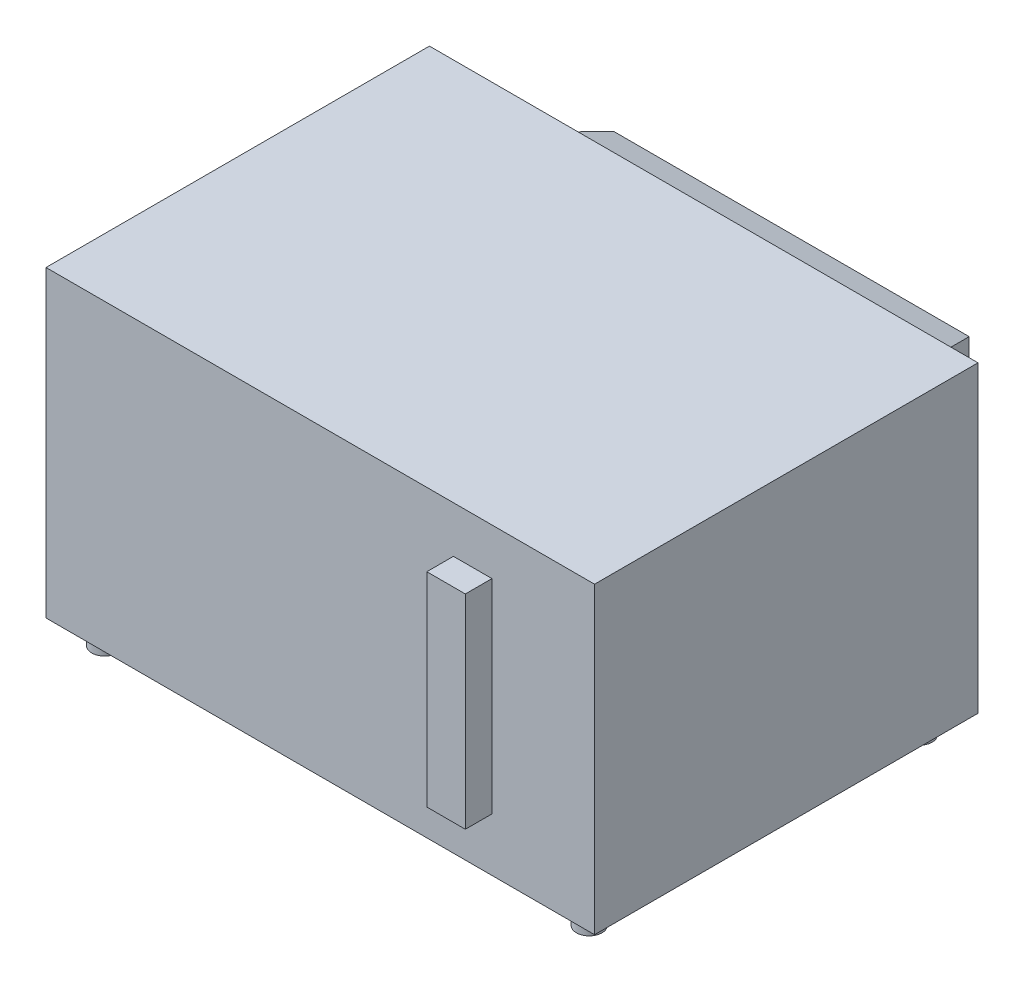
SolidWorks part; units mm, degrees
ref_plane "Спереди" through (0, 0, 0) normal (0, 0, 1) x (1, 0, 0)
ref_plane "Сверху" through (0, 0, 0) normal (0, 1, 0) x (1, 0, 0)
ref_plane "Справа" through (0, 0, 0) normal (1, 0, 0) x (0, 0, -1)
sketch "Эскиз2" plane through (0, 0, 0) normal (0, 1, 0) x (1, 0, 0)
  line L1 (0, 0) -> (515, 0)
  line L2 (0, 0) -> (0, 360)
  line L3 (0, 360) -> (515, 360)
  line L4 (515, 0) -> (515, 360)
extrude "Бобышка-Вытянуть1" add sketch "Эскиз2" along normal blind 285
sketch "Эскиз3" plane through (0, 0, 0) normal (0, -1, 0) x (1, 0, 0)
  line L0 (0, -180) -> (357.8146, -180) construction
  line L1 (0, -360) -> (0, 0) construction
  line L2 (257.5, 0) -> (257.5, -255.9154) construction
  line L3 (0, 0) -> (515, 0) construction
  circle A0 centre (30, -25) radius 12
  circle A1 centre (30, -335) radius 12
  circle A2 centre (485, -335) radius 12
  circle A3 centre (485, -25) radius 12
extrude "Бобышка-Вытянуть2" add sketch "Эскиз3" along normal blind 20
sketch "Эскиз4" plane through (0, 0, 0) normal (0, 0, 1) x (1, 0, 0)
  line L1 (382.5126, 241.3978) -> (418.6878, 241.3978)
  line L2 (382.5126, 241.3978) -> (382.5126, 50.0707)
  line L3 (382.5126, 50.0707) -> (418.6878, 50.0707)
  line L4 (418.6878, 241.3978) -> (418.6878, 50.0707)
  point P4 (418.6878, 50.0707)
extrude "Бобышка-Вытянуть3" add sketch "Эскиз4" along normal blind 25
sketch "Эскиз5" plane through (0, 0, -360) normal (0, 0, -1) x (-1, 0, 0)
  line L1 (-449.3399, 56.097) -> (-60.3753, 56.097)
  line L2 (-449.3399, 56.097) -> (-449.3399, 244.766)
  line L3 (-449.3399, 244.766) -> (-60.3753, 244.766)
  line L4 (-60.3753, 56.097) -> (-60.3753, 244.766)
extrude "Бобышка-Вытянуть4" add sketch "Эскиз5" along normal blind 85 draft 18
